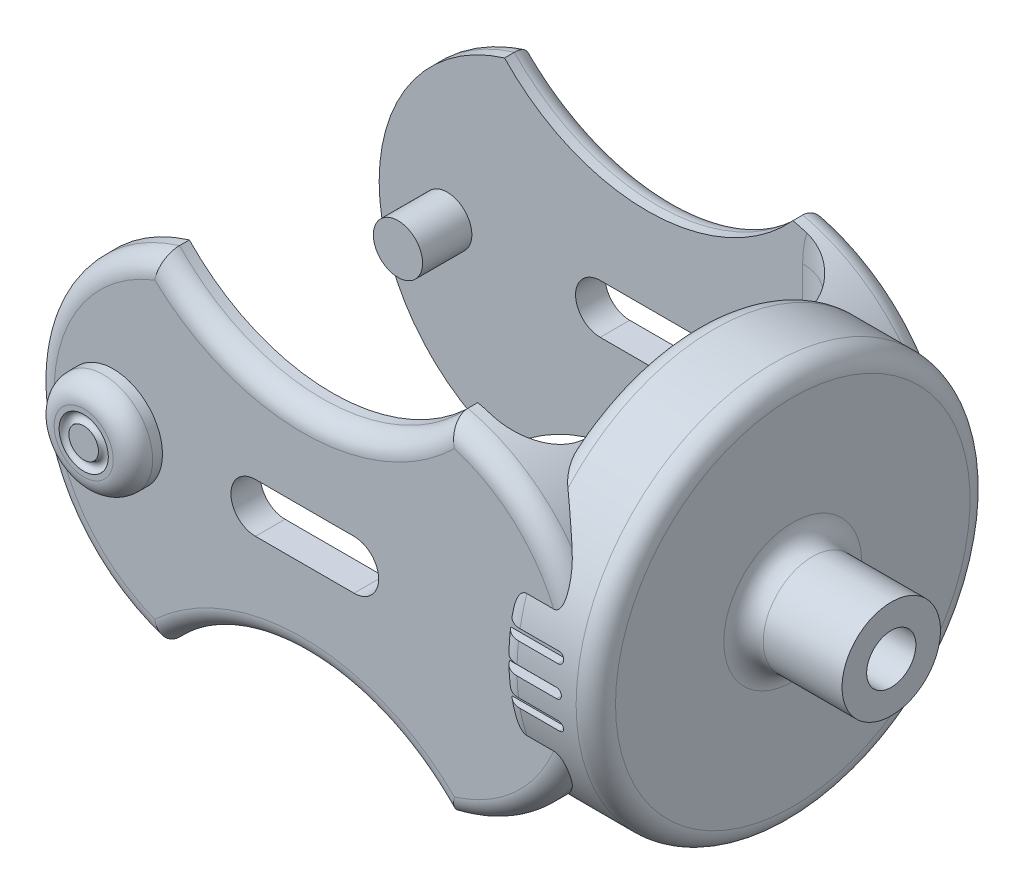
SolidWorks part; units mm, degrees
ref_plane "Front Plane" through (0, 0, 0) normal (0, 0, 1) x (1, 0, 0)
ref_plane "Top Plane" through (0, 0, 0) normal (0, 1, 0) x (1, 0, 0)
ref_plane "Right Plane" through (0, 0, 0) normal (1, 0, 0) x (0, 0, -1)
sketch "Sketch1" plane through (0, 0, 0) normal (0, 0, 1) x (1, 0, 0)
  line L0 (-44.5895, 0) -> (0, 0) construction
  line L1 (0, 5) -> (-10, 5)
  line L2 (-10, 5) -> (-10, 20)
  line L3 (-10, 20) -> (-20, 20)
  line L4 (-20, 20) -> (-20, 15)
  line L5 (-20, 15) -> (-12, 15)
  line L6 (-12, 15) -> (-12, 2.5)
  line L7 (-12, 2.5) -> (0, 2.5)
  line L8 (0, 2.5) -> (0, 5)
  point P11 (-44.5895, 0)
  dimension "D1" = 5
  dimension "D2" = 10
  dimension "D3" = 40
  dimension "D4" = 8
  dimension "D5" = 30
  dimension "D6" = 10
  dimension "D7" = 10
revolve "Revolve1" add sketch "Sketch1" angle 360 about L0
sketch "Sketch2" plane through (-20, 0, 0) normal (-1, 0, 0) x (0, 0, 1)
  line L0 (0, 0) -> (0, 8) construction
  line L1 (-1, 8) -> (-2.9267, 15.1907)
  line L2 (1, 8) -> (2.9267, 15.1907)
  arc A0 (-1, 8) -> (1, 8) centre (0, 8) ccw
  arc A1 (-2.9267, 15.1907) -> (2.9267, 15.1907) centre (0, 1.5) cw
  point P9 (0, 15.5)
  dimension "D2" = 2
  dimension "D4" = 14
  dimension "D1" = 8
  dimension "D3" = 30
  dimension "D5" = 15.5
extrude "Cut-Extrude1" cut sketch "Sketch2" against normal blind 8.5
pattern_circular "CirPattern1" count 8 over 360 about axis through (-20, 0, 0) along (-1, 0, 0) of "Cut-Extrude1"
sketch "Sketch3" plane through (-12, 0, 0) normal (-1, 0, 0) x (0, 0, 1)
  line L1 (0, 4.6188) -> (-4, 2.3094)
  line L2 (-4, 2.3094) -> (-4, -2.3094)
  line L3 (-4, -2.3094) -> (0, -4.6188)
  line L4 (0, -4.6188) -> (4, -2.3094)
  line L5 (4, -2.3094) -> (4, 2.3094)
  line L6 (4, 2.3094) -> (0, 4.6188)
  circle A0 centre (0, 0) radius 4 construction
  dimension "D1" = 8
extrude "Cut-Extrude2" cut sketch "Sketch3" against normal blind 1
fillet "Fillet1" radius 2 3 edges at (-10, 0, 5) (-10, 0, 20) (-20, 0, 20)
sketch "Sketch4" plane through (0, 0, 0) normal (0, 0, 1) x (1, 0, 0)
  line L0 (-30, 0) -> (-50, 0) construction
  line L1 (-30, -18) -> (-50, -18)
  line L2 (-30, 18) -> (-50, 18)
  arc A0 (-30, -18) -> (-30, 18) centre (-30, 0) ccw
  arc A1 (-50, 18) -> (-50, -18) centre (-50, 0) ccw
  point P3 (-40, 0)
  point P8 (-50.4126, 0)
  dimension "D1" = 20
  dimension "D2" = 36
  dimension "D3" = 30
extrude "Boss-Extrude1" add sketch "Sketch4" along normal blind 3 from offset 16
sketch "Sketch5" plane through (0, 0, 19) normal (0, 0, 1) x (1, 0, 0)
  line L0 (-14, 0) -> (-22.8824, 0) construction
  line L1 (0, -5) -> (0, 5) construction
  line L2 (-14, -0.5) -> (-22.8824, -0.5)
  line L3 (-14, 0.5) -> (-22.8824, 0.5)
  arc A0 (-14, -0.5) -> (-14, 0.5) centre (-14, 0) ccw
  arc A1 (-22.8824, 0.5) -> (-22.8824, -0.5) centre (-22.8824, 0) ccw
  point P5 (-18.4412, 0)
  dimension "D1" = 14
extrude "Cut-Extrude3" cut sketch "Sketch5" along normal blind 3
pattern_linear "LPattern4" count 2 spacing 3 along (0, 1, 0) count 2 spacing 3 along (0, -1, 0) of "Cut-Extrude3" pattern seed only yes
sketch "Sketch6" plane through (0, 0, 19) normal (0, 0, 1) x (1, 0, 0)
  line L0 (-40.7834, 31) -> (-40.7834, 18) construction
  line L1 (-30, 18) -> (-50, 18) construction
  circle A0 centre (-40.7834, 31) radius 20
  dimension "D1" = 40
  dimension "D2" = 13
extrude "Cut-Extrude4" cut sketch "Sketch6" against normal blind 3
mirror "Mirror1" about plane through (0, 0, 0) normal (0, 1, 0) of "Cut-Extrude4"
sketch "Sketch7" plane through (0, 0, 19) normal (0, 0, 1) x (1, 0, 0)
  circle A0 centre (-60, 0) radius 5
  arc A1 (-55.2702, 17.2112) -> (-55.2702, -17.2112) centre (-50, 0) ccw construction
  point P7 (-71.9142, 0.9691)
  dimension "D1" = 10
  dimension "D2" = 10
extrude "Boss-Extrude2" add sketch "Sketch7" along normal blind 3
fillet "Fillet2" radius 2 1 edges at (-55, 0, 22)
sketch "Sketch8" plane through (0, 0, 22) normal (0, 0, 1) x (1, 0, 0)
  circle A0 centre (-60, 0) radius 2
  dimension "D1" = 4
sweep "Cut-Sweep1" cut path "Sketch8" circular profile diameter 1 parameters "D3"=1
sketch "Sketch13" plane through (0, 0, 19) normal (0, 0, 1) x (1, 0, 0)
  line L0 (-45.5544, 0) -> (-35.5544, 0) construction
  line L1 (-40.5544, 11.0013) -> (-40.5544, 0) construction
  line L2 (-45.5544, 2.5) -> (-35.5544, 2.5)
  line L3 (-45.5544, -2.5) -> (-35.5544, -2.5)
  arc A0 (-45.5544, 2.5) -> (-45.5544, -2.5) centre (-45.5544, 0) ccw
  arc A1 (-35.5544, -2.5) -> (-35.5544, 2.5) centre (-35.5544, 0) ccw
  arc A3 (-55.2702, 17.2112) -> (-25.9847, 17.5464) centre (-40.7834, 31) ccw construction
  point P3 (0, 0)
  point P5 (-40.5544, 0)
  dimension "D2" = 2.5
  dimension "D1" = 10
extrude "Cut-Extrude5" cut sketch "Sketch13" against normal blind 3
fillet "Fillet3" radius 2 5 edges at (-18.1213, -13.5239, 19) (-40.5544, -11.0013, 19) (-68, 0, 19) (-18.1213, 13.5239, 19) (-40.5544, 11.0013, 19)
fillet "Fillet9" radius 5 3 edges at (-19.4445, 10.9412, 16) (-18.7404, -11.7617, 16) (-20, 0, 16)
sketch "Sketch17" plane through (0, 0, 16) normal (0, 0, -1) x (-1, 0, 0)
  circle A0 centre (61.0894, 0) radius 2.5
  dimension "D1" = 5
extrude "Boss-Extrude3" add sketch "Sketch17" along normal blind 5
mirror "Mirror2" about plane through (0, 0, 0) normal (0, 0, 1) of "LPattern4", "Cut-Extrude5", "Cut-Sweep1", "Boss-Extrude2", "Fillet2", "Mirror1", "Cut-Extrude4", "Cut-Extrude3", "Boss-Extrude1", "Fillet3", "Fillet9", "Boss-Extrude3"
